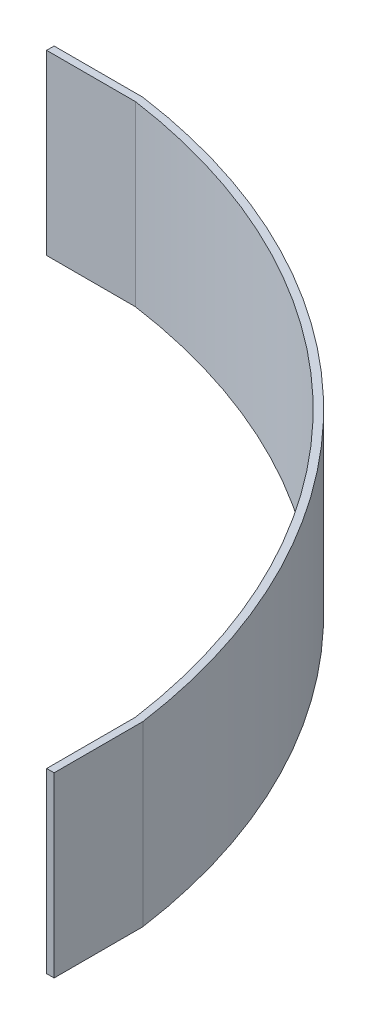
SolidWorks part; units mm, degrees
material "PC High Viscosity"
ref_plane "Front Plane" through (0, 0, 0) normal (0, 0, 1) x (1, 0, 0)
ref_plane "Top Plane" through (0, 0, 0) normal (0, 1, 0) x (1, 0, 0)
ref_plane "Right Plane" through (0, 0, 0) normal (1, 0, 0) x (0, 0, -1)
sketch "Sketch1" plane through (0, 0, 0) normal (0, 1, 0) x (1, 0, 0)
  line L0 (0, 0) -> (0, 133.35) construction
  line L1 (0, 133.35) -> (19.05, 133.35)
  line L2 (0, 0) -> (133.35, 0) construction
  line L3 (133.35, 0) -> (133.35, 19.05)
  line L4 (0, 133.35) -> (0, 134.9534)
  line L5 (0, 134.9534) -> (19.05, 134.9534)
  line L6 (134.9534, 19.05) -> (134.9534, 0)
  line L7 (134.9534, 0) -> (133.35, 0)
  arc A0 (133.35, 19.05) -> (19.05, 133.35) centre (0, 0) ccw
  arc A1 (19.05, 134.9534) -> (134.9534, 19.05) centre (0, 0) cw
  point P9 (0, 0)
  point P12 (0, 0)
  dimension "D5" = 1.5875
  dimension "D1" = 133.35
  dimension "D2" = 19.05
  dimension "D3" = 133.35
  dimension "D4" = 19.05
extrude "Boss-Extrude1" add sketch "Sketch1" along normal blind 38.1 contours A1 L5 L4 L1 A0 L3 L7 L6 region at (1.9085, 0, -134.1517)
